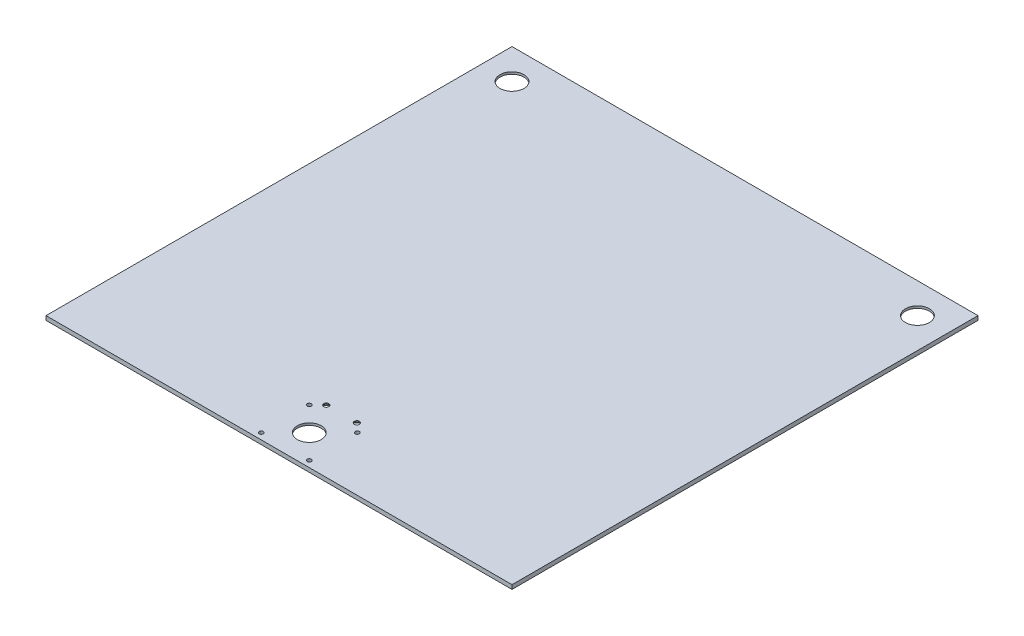
SolidWorks part; units mm, degrees
material "6061-T6 (SS)"
ref_plane "Front Plane" through (0, 0, 0) normal (0, 0, 1) x (1, 0, 0)
ref_plane "Top Plane" through (0, 0, 0) normal (0, 1, 0) x (1, 0, 0)
ref_plane "Right Plane" through (0, 0, 0) normal (1, 0, 0) x (0, 0, -1)
sketch "Sketch1" plane through (0, 0, 0) normal (0, 1, 0) x (1, 0, 0)
  line L1 (-228.6, -228.6) -> (228.6, -228.6)
  line L2 (-228.6, -228.6) -> (-228.6, 228.6)
  line L3 (-228.6, 228.6) -> (228.6, 228.6)
  line L4 (228.6, -228.6) -> (228.6, 228.6)
  line L5 (-228.6, -228.6) -> (228.6, 228.6) construction
  line L6 (-228.6, 228.6) -> (228.6, -228.6) construction
  point P0 (0, 0)
  dimension "D1" = 457.2
  dimension "D2" = 457.2
extrude "Boss-Extrude1" add sketch "Sketch1" along normal blind 4.064
sketch "Sketch2" plane through (0, 0, 0) normal (0, -1, 0) x (1, 0, 0)
  line L0 (0, -2.2352) -> (0, 2.2352) construction
  line L1 (-228.6, 228.6) -> (228.6, 228.6) construction
  line L2 (-228.6, -228.6) -> (-228.6, 228.6) construction
  line L3 (228.6, -228.6) -> (-228.6, -228.6) construction
  line L4 (228.6, 228.6) -> (228.6, -228.6) construction
  circle A0 centre (0, 198.882) radius 19.177
  circle A1 centre (-198.882, -198.882) radius 19.177
  circle A2 centre (198.882, -198.882) radius 19.177
  dimension "D1" = 38.354
  dimension "D3" = 38.354
  dimension "D4" = 38.354
  dimension "D2" = 29.718
  dimension "D5" = 29.718
  dimension "D6" = 29.718
  dimension "D7" = 29.718
  dimension "D8" = 29.718
extrude "Cut-Extrude1" cut sketch "Sketch2" against normal blind 1.905
sketch "Sketch3" plane through (0, 1.905, 0) normal (0, -1, 0) x (1, 0, 0)
  circle A0 centre (0, 198.882) radius 11.7475
  circle A1 centre (0, 198.882) radius 19.177 construction
  circle A2 centre (-198.882, -198.882) radius 11.7475
  circle A3 centre (198.882, -198.882) radius 11.7475
  circle A4 centre (198.882, -198.882) radius 19.177 construction
  circle A5 centre (-198.882, -198.882) radius 19.177 construction
  dimension "D1" = 23.495
  dimension "D2" = 23.495
  dimension "D3" = 23.495
extrude "Cut-Extrude2" cut sketch "Sketch3" against normal up to next
hole_wizard "#10-32 Tapped Hole1" positions "Sketch7" profile "Sketch8" tap size "#10-32" standard "ANSI Inch" end condition through all
sketch "Sketch7" plane through (0, 0, 0) normal (0, -1, 0) x (-1, 0, 0.0002)
  point P0 (23.6171, -222.4505)
  point P1 (-23.5293, -222.4598)
sketch "Sketch8" plane through (-23.5732, 0, 222.4552) normal (1, 0, 0) x (0, 0, -1)
  line L0 (0, 0) -> (0, 4.064)
  line L1 (0, 4.064) -> (2.0193, 4.064)
  line L2 (2.0193, 4.064) -> (2.0193, 0)
  line L3 (2.0193, 0) -> (0, 0)
  line L4 (0, -6.35) -> (0, 107.95) construction
  dimension "Thru Tap Drill Dia." = 4.0386
  dimension "Thru Tap Drill Depth" = 4.064
cosmetic thread "Hole Thread1" parameters "D1"=4.7625, "D2"=4.826
cosmetic thread "Hole Thread2" parameters "D1"=4.7625, "D2"=4.826
hole_wizard "#10-32 Tapped Hole2" positions "Sketch9" profile "Sketch10" tap size "#10-32" standard "ANSI Inch" end condition through all
sketch "Sketch9" plane through (0, 0, 0) normal (0, -1, 0) x (-1, 0, 0.0002)
  point P0 (23.6078, -175.3042)
  point P1 (-23.5386, -175.3135)
sketch "Sketch10" plane through (-23.5732, 0, 175.3088) normal (1, 0, 0) x (0, 0, -1)
  line L0 (0, 0) -> (0, 4.064)
  line L1 (0, 4.064) -> (2.0193, 4.064)
  line L2 (2.0193, 4.064) -> (2.0193, 0)
  line L3 (2.0193, 0) -> (0, 0)
  line L4 (0, -6.35) -> (0, 107.95) construction
  dimension "Thru Tap Drill Dia." = 4.0386
  dimension "Thru Tap Drill Depth" = 4.064
cosmetic thread "Hole Thread3" parameters "D1"=4.7625, "D2"=4.826
cosmetic thread "Hole Thread4" parameters "D1"=4.7625, "D2"=4.826
hole_wizard "CBORE for #10 Binding Head Machine Screw1" positions "Sketch11" profile "Sketch12" counterbore size "#10" standard "ANSI Inch" end condition through all
sketch "Sketch11" plane through (0, 0, 0) normal (0, -1, 0) x (1, 0, 0)
  point P0 (-15, 167.1745)
  point P1 (15, 167.1745)
sketch "Sketch12" plane through (-15, 0, 167.1745) normal (1, 0, 0) x (0, 0, -1)
  line L0 (0, 0) -> (0, 4.064)
  line L1 (0, 4.064) -> (2.5527, 4.064)
  line L2 (2.5527, 4.064) -> (2.5527, 3.1242)
  line L3 (2.5527, 3.1242) -> (5.5562, 3.1242)
  line L4 (5.5562, 3.1242) -> (5.5562, 0)
  line L5 (5.5562, 0) -> (0, 0)
  line L6 (0, -6.35) -> (0, 107.95) construction
  dimension "Thru Hole Dia." = 5.1054
  dimension "Thru Hole Depth" = 4.064
  dimension "C'Bore Dia." = 11.1125
  dimension "C'Bore Depth" = 3.1242
